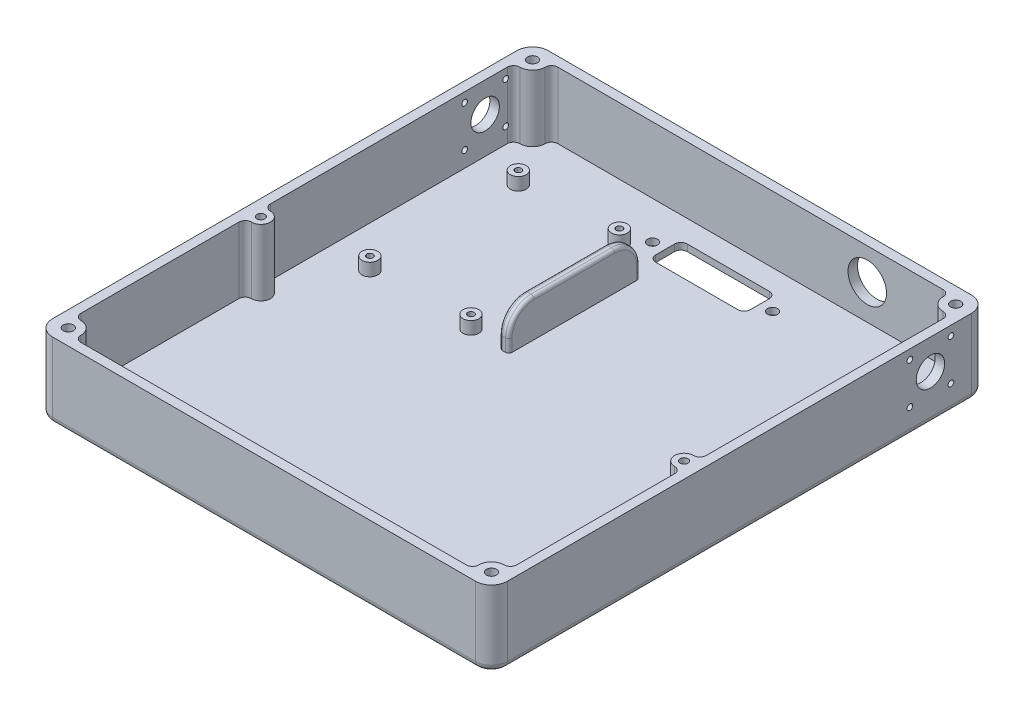
SolidWorks part; units mm, degrees
ref_plane "前视基准面" through (0, 0, 0) normal (0, 0, 1) x (1, 0, 0)
ref_plane "上视基准面" through (0, 0, 0) normal (0, 1, 0) x (1, 0, 0)
ref_plane "右视基准面" through (0, 0, 0) normal (1, 0, 0) x (0, 0, -1)
sketch "草图1" plane through (0, 0, 0) normal (0, 1, 0) x (1, 0, 0)
  line L1 (-72, -78.5) -> (72, -78.5)
  line L2 (-72, -78.5) -> (-72, 78.5)
  line L3 (-72, 78.5) -> (72, 78.5)
  line L4 (72, -78.5) -> (72, 78.5)
  line L5 (-72, -78.5) -> (72, 78.5) construction
  line L6 (-72, 78.5) -> (72, -78.5) construction
  point P0 (0, 0)
  dimension "D1" = 144
  dimension "D2" = 157
extrude "凸台-拉伸1" add sketch "草图1" along normal blind 24
sketch "草图2" plane through (0, 24, 0) normal (0, 1, 0) x (1, 0, 0)
  line L8 (69, 75.5) -> (-69, 75.5)
  line L9 (-69, 75.5) -> (-69, -75.5)
  line L10 (-69, -75.5) -> (69, -75.5)
  line L11 (69, -75.5) -> (69, 75.5)
  line L12 (69, 75.5) -> (-69, 75.5)
  line L13 (-69, 75.5) -> (-69, -75.5)
  line L14 (-69, -75.5) -> (69, -75.5)
  line L15 (69, -75.5) -> (69, 75.5)
  dimension "D1" = 3
extrude "切除-拉伸1" cut sketch "草图2" against normal blind 21
sketch "草图4" plane through (0, 3, 0) normal (0, 1, 0) x (1, 0, 0)
  line L0 (-67, 73.5) -> (-67, -12.5) construction
  line L1 (-67, -12.5) -> (67, -12.5) construction
  line L2 (67, -12.5) -> (-67, 73.5) construction
  line L5 (69, 75.5) -> (-69, 75.5) construction
  line L6 (-69, 75.5) -> (-69, -75.5) construction
  line L7 (69, -75.5) -> (69, 75.5) construction
  line L8 (-69, -75.5) -> (69, -75.5) construction
  line L9 (69, -75.5) -> (69, 75.5) construction
  line L10 (-69, -75.5) -> (69, -75.5) construction
  circle A0 centre (67, 73.5) radius 4
  circle A1 centre (-67, -12.5) radius 3
  circle A2 centre (-67, 73.5) radius 4
  circle A3 centre (67, -12.5) radius 3
  circle A4 centre (-67, -73.5) radius 4
  circle A5 centre (67, -73.5) radius 4
  dimension "D4" = 8
  dimension "D2" = 8
  dimension "D8" = 6
  dimension "D9" = 2
  dimension "D10" = 6
  dimension "D13" = 8
  dimension "D14" = 8
  dimension "D3" = 63
  dimension "D5" = 2
  dimension "D6" = 2
  dimension "D7" = 2
  dimension "D1" = 2
  dimension "D11" = 2
  dimension "D12" = 2
extrude "凸台-拉伸3" add sketch "草图4" along normal up to surface (21 mm away) up to face at (0, 24, 0)
sketch "草图5" plane through (0, 24, 0) normal (0, 1, 0) x (1, 0, 0)
  line L0 (-72, 78.5) -> (-72, -78.5) construction
  line L1 (-67, -9.5) -> (-72, -9.5)
  line L2 (-67, -9.5) -> (-67, -15.5)
  line L3 (-67, -15.5) -> (-72, -15.5)
  line L4 (-72, -9.5) -> (-72, -15.5)
  line L5 (-67, 69.5) -> (-70.7143, 69.5)
  line L6 (-70.7143, 69.5) -> (-70.7143, 75.7158)
  line L7 (-70.7143, 75.7158) -> (-63, 77.6726)
  line L8 (-63, 77.6726) -> (-63, 73.5)
  line L9 (-63, 73.5) -> (-67, 69.5)
  line L10 (0, 0) -> (0, 48.5546) construction
  line L11 (63, 73.5) -> (67, 69.5)
  line L12 (63, 77.6726) -> (63, 73.5)
  line L13 (70.7143, 75.7158) -> (63, 77.6726)
  line L14 (70.7143, 69.5) -> (70.7143, 75.7158)
  line L15 (67, 69.5) -> (70.7143, 69.5)
  line L16 (72, -9.5) -> (72, -15.5)
  line L17 (67, -15.5) -> (72, -15.5)
  line L18 (67, -9.5) -> (67, -15.5)
  line L19 (67, -9.5) -> (72, -9.5)
  arc A0 (-69, -14.7361) -> (-69, -10.2639) centre (-67, -12.5) ccw construction
  arc A1 (-69, -14.7361) -> (-69, -10.2639) centre (-67, -12.5) ccw construction
  arc A2 (-69, 70.0359) -> (-63.5359, 75.5) centre (-67, 73.5) ccw construction
  arc A3 (-69, 70.0359) -> (-63.5359, 75.5) centre (-67, 73.5) ccw construction
  arc A4 (-69, 70.0359) -> (-63.5359, 75.5) centre (-67, 73.5) ccw construction
  arc A5 (-69, -14.7361) -> (-69, -10.2639) centre (-67, -12.5) ccw construction
extrude "凸台-拉伸4" add sketch "草图5" against normal up to next
hole_wizard "Ø3.2 (3.2) 直径孔1" positions "草图7" profile "草图6" hole size "Ø3.2" standard "ANSI Metric"
sketch "草图7" plane through (0, 24, 0) normal (0, 1, 0) x (-1, 0, 0)
  point P0 (67, -73.5)
  point P1 (-67, -73.5)
  point P4 (-67, 12.5)
  point P7 (67, 12.5)
sketch "草图6" plane through (-67, 24, -73.5) normal (1, 0, 0) x (0, 0, 1)
  line L0 (0, 0) -> (0, 5.9614)
  line L1 (0, 5.9614) -> (1.6, 5)
  line L2 (1.6, 5) -> (1.6, 0)
  line L5 (1.6, 0) -> (0, 0)
  line L10 (0, 5.9614) -> (-1.6, 5) construction
  line L11 (0, -6.35) -> (0, 107.95) construction
  dimension "孔直径" = 3.2
  dimension "孔深度" = 5
  dimension "导头角度" = 118
sketch "草图8" plane through (0, 3, 0) normal (0, 1, 0) x (1, 0, 0)
  line L0 (-69, -15.5) -> (0, -15.5) construction
  line L1 (-50, -17) -> (50, -17)
  line L2 (-50, -17) -> (-50, -14)
  line L3 (-50, -14) -> (50, -14)
  line L4 (50, -17) -> (50, -14)
  line L5 (-50, -17) -> (50, -14) construction
  line L6 (-50, -14) -> (50, -17) construction
  line L7 (0, -15.5) -> (0, 0) construction
  line L8 (69, -9.5) -> (69, 69.5) construction
  line L9 (-14, 10) -> (-11, 10)
  line L10 (-14, 10) -> (-14, 51.5)
  line L11 (-14, 51.5) -> (-11, 51.5)
  line L12 (-11, 10) -> (-11, 51.5)
  line L13 (-69, -15.5) -> (-69, -70.0359) construction
  line L14 (63, 75.5) -> (-63, 75.5) construction
  point P0 (0, -15.5)
  dimension "D1" = 3
  dimension "D2" = 100
  dimension "D3" = 3
  dimension "D4" = 80
  dimension "D5" = 24
  dimension "D6" = 24
  dimension "D7" = 14
extrude "凸台-拉伸5" add sketch "草图8" along normal blind 12
fillet "圆角3" radius 8 4 edges at (50, 15, 15.5) (-50, 15, 15.5) (-12.5, 15, -10) (-12.5, 15, -51.5)
fillet "圆角4" radius 1 20 edges at (50, 5, 14) (47.6569, 12.6569, 14) (-50, 5, 14) (-47.6569, 12.6569, 14) (-50, 5, 17) (-47.6569, 12.6569, 17) (50, 5, 17) (47.6569, 12.6569, 17) (0, 15, 14) (0, 15, 17) (-11, 5, -10) (-11, 12.6569, -12.3431) (-11, 5, -51.5) (-11, 12.6569, -49.1569) (-14, 5, -51.5) (-14, 12.6569, -49.1569) (-14, 5, -10) (-14, 12.6569, -12.3431) (-11, 15, -30.75) (-14, 15, -30.75)
sketch "草图9" plane through (-72, 0, 0) normal (-1, 0, 0) x (0, 0, 1)
  line L0 (-78.5, 24) -> (78.5, 24) construction
  line L2 (-60.5, 0) -> (-60.5, 5) construction
  line L3 (-78.5, 0) -> (78.5, 0) construction
  line L4 (-60.5, 5) -> (-60.5, 24) construction
  line L5 (-69.5, 24) -> (-69.5, 3) construction
  circle A0 centre (-60.5, 14.5) radius 4.5
  dimension "D1" = 5
  dimension "D2" = 9
  dimension "D3" = 9
extrude "切除-拉伸2" cut sketch "草图9" against normal blind 10
sketch "草图12" plane through (0, 3, 0) normal (0, 1, 0) x (1, 0, 0)
  line L0 (0, 0) -> (0, 63.5) construction
  line L1 (-15, 58.5) -> (15, 58.5)
  line L2 (-15, 58.5) -> (-15, 68.5)
  line L3 (-15, 68.5) -> (15, 68.5)
  line L4 (15, 58.5) -> (15, 68.5)
  line L5 (-15, 58.5) -> (15, 68.5) construction
  line L6 (-15, 68.5) -> (15, 58.5) construction
  line L8 (72, 78.5) -> (-72, 78.5) construction
  point P0 (0, 63.5)
  dimension "D1" = 10
  dimension "D2" = 30
  dimension "D4" = 15
extrude "切除-拉伸3" cut sketch "草图12" against normal blind 12
sketch "草图13" plane through (0, 0, 0) normal (0, -1, 0) x (1, 0, 0)
  line L0 (0, -68.5) -> (0, -58.5) construction
  line L1 (-22, -70) -> (22, -70)
  line L2 (-22, -70) -> (-22, -57)
  line L3 (-22, -57) -> (22, -57)
  line L4 (22, -70) -> (22, -57)
  line L5 (-22, -70) -> (22, -57) construction
  line L6 (-22, -57) -> (22, -70) construction
  line L7 (-15, -68.5) -> (15, -68.5) construction
  line L8 (15, -58.5) -> (-15, -58.5) construction
  point P0 (0, -63.5)
  dimension "D1" = 44
  dimension "D2" = 13
extrude "切除-拉伸4" cut sketch "草图13" against normal blind 0.9
fillet "圆角5" radius 1.75 4 edges at (22, 0.45, -70) (22, 0.45, -57) (-22, 0.45, -70) (-22, 0.45, -57)
sketch "草图14" plane through (0, 0.9, 0) normal (0, -1, 0) x (1, 0, 0)
  line L0 (0, -58.5) -> (0, -68.5) construction
  line L1 (15, -68.5) -> (-15, -68.5) construction
  line L2 (-15, -58.5) -> (15, -58.5) construction
  line L3 (-19, -63.5) -> (19, -63.5) construction
  circle A0 centre (-19, -63.5) radius 1.6
  circle A1 centre (19, -63.5) radius 1.6
  point P8 (0, -63.5)
  dimension "D1" = 3.2
  dimension "D2" = 38
extrude "切除-拉伸5" cut sketch "草图14" against normal blind 1
sketch "草图15" plane through (0, 1.9, 0) normal (0, -1, 0) x (1, 0, 0)
  circle A0 centre (-19, -63.5) radius 1.6
  circle A1 centre (19, -63.5) radius 1.6
  dimension "D1" = 3.2
extrude "切除-拉伸6" cut sketch "草图15" against normal blind 3
sketch "草图17" plane through (0, 3, 0) normal (0, 1, 0) x (1, 0, 0)
  line L1 (-56, 58) -> (-56, 11) construction
  line L2 (-56, 11) -> (-24, 11) construction
  line L3 (-24, 11) -> (-56, 58) construction
  line L4 (-14, 50.5) -> (-14, 11) construction
  line L5 (49, -14) -> (-49, -14) construction
  circle A0 centre (-56, 58) radius 2.5
  circle A1 centre (-24, 58) radius 2.5
  circle A2 centre (-56, 11) radius 2.5
  circle A3 centre (-24, 11) radius 2.5
  dimension "D3" = 47
  dimension "D4" = 32
  dimension "D5" = 25
  dimension "D6" = 10
  dimension "D7" = 5
  dimension "D1" = 2
  dimension "D2" = 2
extrude "凸台-拉伸6" add sketch "草图17" along normal blind 4
fillet "圆角8" radius 2 7 edges at (-69, 13.5, -69.5) (-69, 13.5, 15.5) (69, 13.5, 15.5) (63, 13.5, -75.5) (69, 13.5, -69.5) (69, 13.5, 9.5) (-69, 13.5, 9.5)
hole_wizard "Ø1.7 (1.7) 直径孔3" positions "草图19" profile "草图18" hole size "Ø1.7" standard "ANSI Metric"
sketch "草图19" plane through (0, 7, 0) normal (0, 1, 0) x (-1, 0, 0)
  point P0 (56, -58)
  point P1 (24, -58)
  point P4 (24, -11)
  point P7 (56, -11)
sketch "草图18" plane through (-56, 7, -58) normal (1, 0, 0) x (0, 0, 1)
  line L0 (0, 0) -> (0, 5.6009)
  line L1 (0, 5.6009) -> (1, 5)
  line L2 (1, 5) -> (1, 0)
  line L5 (1, 0) -> (0, 0)
  line L10 (0, 5.6009) -> (-1, 5) construction
  line L11 (0, -6.35) -> (0, 107.95) construction
  dimension "孔直径" = 2
  dimension "孔深度" = 5
  dimension "导头角度" = 118
hole_wizard "Ø1.8 (1.8) 直径孔1" positions "草图11" profile "草图10" hole size "Ø1.8" standard "ANSI Metric"
sketch "草图11" plane through (-72, 0, 0) normal (-1, 0, 0) x (0, 0, 1)
  line L0 (-67, 21) -> (-54, 8) construction
  line L1 (-54, 8) -> (-54, 21) construction
  line L2 (-54, 21) -> (-67, 21) construction
  circle A0 centre (-60.5, 14.5) radius 4.5 construction
  point P0 (-67, 21)
  point P6 (-54, 21)
  point P7 (-67, 8)
  point P8 (-54, 8)
  dimension "D3" = 6.5
  dimension "D4" = 6.5
  dimension "D5" = 13
  dimension "D1" = 2
  dimension "D2" = 2
sketch "草图10" plane through (-72, 21, -67) normal (0, 1, 0) x (0, 0, 1)
  line L0 (0, 0) -> (0, 5.5408)
  line L1 (0, 5.5408) -> (0.9, 5)
  line L2 (0.9, 5) -> (0.9, 0)
  line L5 (0.9, 0) -> (0, 0)
  line L10 (0, 5.5408) -> (-0.9, 5) construction
  line L11 (0, -6.35) -> (0, 107.95) construction
  dimension "孔直径" = 1.8
  dimension "孔深度" = 5
  dimension "导头角度" = 118
mirror "镜向1" about plane through (0, 0, 0) normal (1, 0, 0) of "Ø1.8 (1.8) 直径孔1", "切除-拉伸2"
fillet "圆角9" radius 2 1 edges at (0, 0, 78.5)
fillet "圆角10" radius 2 4 edges at (-15, 1.95, -68.5) (-15, 1.95, -58.5) (15, 1.95, -68.5) (15, 1.95, -58.5)
fillet "圆角13" radius 5 4 edges at (72, 13, 78.5) (-72, 13, 78.5) (-72, 12, -78.5) (72, 12, -78.5)
fillet "圆角15" radius 2 1 edges at (-63, 13.5, -75.5)
sketch "草图20" plane through (0, 3, 0) normal (0, 1, 0) x (1, 0, 0)
  line L0 (-67, -69.5) -> (-69, -69.5)
  line L1 (-63, -73.5) -> (-63, -75.5)
  line L2 (63, -73.5) -> (63, -75.5)
  line L3 (67, -69.5) -> (69, -69.5)
  line L4 (63, -75.5) -> (63.5359, -75.5)
  line L6 (61, 75.5) -> (-61, 75.5)
  line L7 (-69, 67.5) -> (-69, -7.5)
  line L8 (-69, -17.5) -> (-69, -70.0359)
  line L9 (-63.5359, -75.5) -> (63.5359, -75.5)
  line L10 (69, -70.0359) -> (69, -17.5)
  line L11 (69, -7.5) -> (69, 67.5)
  line L14 (-69, -69.5) -> (-69, -70.0359)
  line L15 (-63.5359, -75.5) -> (-63, -75.5)
  line L16 (69, -70.0359) -> (69, -69.5)
  arc A14 (-61, 75.5) -> (-63, 73.5) centre (-61, 73.5) ccw
  arc A15 (-67, 69.5) -> (-63, 73.5) centre (-67, 73.5) ccw
  arc A16 (-67, 69.5) -> (-69, 67.5) centre (-67, 67.5) ccw
  arc A17 (-69, -7.5) -> (-67, -9.5) centre (-67, -7.5) ccw
  arc A18 (-67, -15.5) -> (-67, -9.5) centre (-67, -12.5) ccw
  arc A19 (-67, -15.5) -> (-69, -17.5) centre (-67, -17.5) ccw
  arc A20 (-63.5359, -75.5) -> (-69, -70.0359) centre (-67, -73.5) ccw
  arc A21 (69, -70.0359) -> (63.5359, -75.5) centre (67, -73.5) ccw
  arc A22 (69, -17.5) -> (67, -15.5) centre (67, -17.5) ccw
  arc A23 (67, -9.5) -> (67, -15.5) centre (67, -12.5) ccw
  arc A24 (67, -9.5) -> (69, -7.5) centre (67, -7.5) ccw
  arc A25 (69, 67.5) -> (67, 69.5) centre (67, 67.5) ccw
  arc A26 (63, 73.5) -> (67, 69.5) centre (67, 73.5) ccw
  arc A27 (63, 73.5) -> (61, 75.5) centre (61, 73.5) ccw
  arc A34 (-63.5359, -75.5) -> (-69, -70.0359) centre (-67, -73.5) ccw
  arc A35 (69, -70.0359) -> (63.5359, -75.5) centre (67, -73.5) ccw
  line M49 (-69, -17.5) -> (-69, -70.0359)
  arc M50 (-69, -70.0359) -> (-63.5359, -75.5) centre (-67, -73.5) cw
  line M51 (-63.5359, -75.5) -> (63.5359, -75.5)
  arc M52 (63.5359, -75.5) -> (69, -70.0359) centre (67, -73.5) cw
  line M53 (69, -70.0359) -> (69, -17.5)
  dimension "D1" = 0
extrude "凸台-拉伸7" add sketch "草图20" along normal up to surface (21 mm away) contours L0 M50 M49 | L1 M50 M51 | L3 M52 M53 | L2 M52 M51 up to face at (-67, 24, -71.9)
fillet "圆角16" radius 2 4 edges at (69, 13.5, 69.5) (63, 13.5, 75.5) (-63, 13.5, 75.5) (-69, 13.5, 69.5)
hole_wizard "Ø3.2 (3.2) 直径孔2" positions "草图22" profile "草图21" hole size "Ø3.2" standard "ANSI Metric"
sketch "草图22" plane through (0, 24, 0) normal (0, 1, 0) x (-1, 0, 0)
  point P0 (67, 73.5)
  point P3 (-67, 73.5)
sketch "草图21" plane through (-67, 24, 73.5) normal (1, 0, 0) x (0, 0, 1)
  line L0 (0, 0) -> (0, 5.9614)
  line L1 (0, 5.9614) -> (1.6, 5)
  line L2 (1.6, 5) -> (1.6, 0)
  line L5 (1.6, 0) -> (0, 0)
  line L10 (0, 5.9614) -> (-1.6, 5) construction
  line L11 (0, -6.35) -> (0, 107.95) construction
  dimension "孔直径" = 3.2
  dimension "孔深度" = 5
  dimension "导头角度" = 118
fillet "圆角17" radius 2 7 edges at (71.7434, 0, 75.0811) (72, 0, 0) (70.5355, 0, -77.0355) (-71.7434, 0, 75.0811) (-72, 0, 0) (-70.5355, 0, -77.0355) (0, 0, -78.5)
sketch "草图23" plane through (0, 0, 0) normal (0, -1, 0) x (1, 0, 0)
  line L0 (-67, -73.5) -> (-67, -76.329) construction
  line L1 (-67, -76.329) -> (-64.55, -74.9145)
  line L2 (-64.55, -74.9145) -> (-64.55, -72.0855)
  line L3 (-64.55, -72.0855) -> (-67, -70.671)
  line L4 (-67, -70.671) -> (-69.45, -72.0855)
  line L5 (-69.45, -72.0855) -> (-69.45, -74.9145)
  line L6 (-69.45, -74.9145) -> (-67, -76.329)
  line L7 (0, 0) -> (0, -76.5) construction
  line L8 (-67, -76.5) -> (67, -76.5) construction
  line L9 (0, 0) -> (-70, 0) construction
  line L10 (-70, 73.5) -> (-70, -73.5) construction
  line L11 (67, -76.329) -> (64.55, -74.9145)
  line L12 (64.55, -74.9145) -> (64.55, -72.0855)
  line L13 (64.55, -72.0855) -> (67, -70.671)
  line L14 (67, -70.671) -> (69.45, -72.0855)
  line L15 (69.45, -72.0855) -> (69.45, -74.9145)
  line L16 (69.45, -74.9145) -> (67, -76.329)
  line L17 (-67, 76.329) -> (-64.55, 74.9145)
  line L18 (-69.45, 74.9145) -> (-67, 76.329)
  line L19 (-69.45, 72.0855) -> (-69.45, 74.9145)
  line L20 (-67, 70.671) -> (-69.45, 72.0855)
  line L21 (-64.55, 72.0855) -> (-67, 70.671)
  line L22 (-64.55, 74.9145) -> (-64.55, 72.0855)
  line L23 (69.45, 74.9145) -> (67, 76.329)
  line L24 (69.45, 72.0855) -> (69.45, 74.9145)
  line L25 (67, 70.671) -> (69.45, 72.0855)
  line L26 (64.55, 72.0855) -> (67, 70.671)
  line L27 (64.55, 74.9145) -> (64.55, 72.0855)
  line L28 (67, 76.329) -> (64.55, 74.9145)
  circle A0 centre (67, -73.5) radius 1.6 construction
  circle A1 centre (67, -73.5) radius 1.6 construction
  circle A2 centre (-67, -73.5) radius 1.6 construction
  circle A3 centre (-67, -73.5) radius 1.6 construction
  circle A4 centre (67, 73.5) radius 1.6 construction
  circle A5 centre (67, 73.5) radius 1.6 construction
  circle A6 centre (-67, 73.5) radius 1.6 construction
  circle A7 centre (-67, 73.5) radius 1.6 construction
  circle A8 centre (-67, -73.5) radius 2.45 construction
  dimension "D1" = 4.9
extrude "切除-拉伸7" cut sketch "草图23" against normal blind 20
sketch "草图24" plane through (0, 15, 0) normal (0, 1, 0) x (1, 0, 0)
  line L0 (-42, -16) -> (42, -16) construction
  line L1 (52.3204, -26.584) -> (-52.3204, -26.584)
  line L2 (52.3204, -26.584) -> (52.3204, -5.416)
  line L3 (52.3204, -5.416) -> (-52.3204, -5.416)
  line L4 (-52.3204, -26.584) -> (-52.3204, -5.416)
  line L5 (52.3204, -26.584) -> (-52.3204, -5.416) construction
  line L6 (52.3204, -5.416) -> (-52.3204, -26.584) construction
  point P0 (0, -16)
extrude "切除-拉伸8" cut sketch "草图24" against normal up to surface (12 mm away) up to face at (-56, 3, -8.5)
sketch "草图25" plane through (0, 0, -78.5) normal (0, 0, -1) x (-1, 0, 0)
  line L0 (-72, 2) -> (-72, 24) construction
  line L1 (-67, 24) -> (67, 24) construction
  circle A0 centre (-37, 14) radius 6.1
  dimension "D1" = 12.2
  dimension "D3" = 10
  dimension "D2" = 35
extrude "切除-拉伸9" cut sketch "草图25" against normal blind 10
sketch "草图26" plane through (0, 24, 0) normal (0, 1, 0) x (1, 0, 0)
  circle A0 centre (-67, -12.5) radius 1.6 construction
  circle A1 centre (-67, -12.5) radius 1.6
  circle A2 centre (67, -12.5) radius 1.6 construction
  circle A3 centre (67, -12.5) radius 1.6
  circle A4 centre (-67, -12.5) radius 1.25
  circle A5 centre (67, -12.5) radius 1.25
  dimension "D1" = 2.5
extrude "凸台-拉伸8" add sketch "草图26" against normal blind 10
